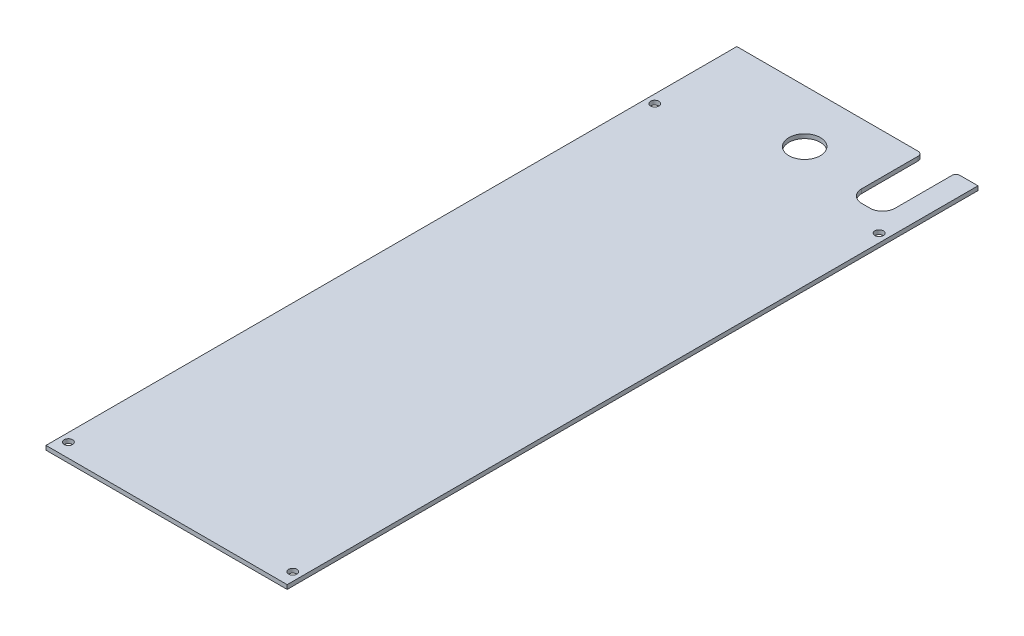
SolidWorks part; units mm, degrees
note: The reader was unsure of these and kept them because the rebuilt part matched: thickness of "Brida base2", "Chapa metálica(12)", "Chapa metálica(21)", "Chapa metálica(22)", "Chapa metálica(23)".
material "Poliestireno"
ref_plane "Alzado" through (0, 0, 0) normal (0, 0, 1) x (1, 0, 0)
ref_plane "Planta" through (0, 0, 0) normal (0, 1, 0) x (1, 0, 0)
ref_plane "Vista lateral" through (0, 0, 0) normal (1, 0, 0) x (0, 0, -1)
sketch "Croquis12" plane through (0, 0, 0) normal (0, 1, 0) x (1, 0, 0)
  line L0 (0, 0) -> (0, 121.41) construction
  line L1 (-57.5, -207.99) -> (57.5, -207.99)
  line L2 (-57.5, -207.99) -> (-57.5, 121.41)
  line L3 (-57.5, 121.41) -> (57.5, 121.41)
  line L4 (57.5, -207.99) -> (57.5, 121.41)
  point P14 (57.5, 121.41)
  point P17 (-57.5, 121.41)
  dimension "D1" = 115
  dimension "D2" = 207.99
  dimension "D3" = 121.41
base flange "Brida base2" sketch "Croquis12" thickness 2 reverse thickness direction no parameters "D1"=1
sketch "Croquis25" plane through (0, 0, 0) normal (0, 1, 0) x (1, 0, 0)
  line L0 (0, 0) -> (0, -48.7685) construction
  line L2 (-159.058, -201.3) -> (150.1867, -201.3) construction
  dimension "D2" = 201.3
sketch "Croquis27" plane through (0, 0, 0) normal (0, 1, 0) x (1, 0, 0)
  line L0 (0, 0) -> (0, -88.775) construction
  line L1 (-159.058, -201.3) -> (150.1867, -201.3) construction
  circle A0 centre (-53.5, -201.3) radius 2
  circle A1 centre (-53.5, 78.26) radius 2
  circle A2 centre (53.5, 78.26) radius 2
  circle A3 centre (53.5, -201.3) radius 2
  dimension "D1" = 4
  dimension "D4" = 107
  dimension "D2" = 78.26
extrude "Cortar-Extruir6" cut sketch "Croquis27" against normal up to next normal cut yes
sketch "Croquis28" plane through (0, 0, 0) normal (0, 1, 0) x (1, 0, 0)
  line L1 (-57.5, -207.99) -> (57.5, -207.99) construction
  circle A0 centre (0, 96.25) radius 7.5
  dimension "D1" = 304.24
  dimension "D2" = 15
extrude "Cortar-Extruir7" cut sketch "Croquis28" against normal up to next normal cut yes
sketch "Croquis29" plane through (0, 0, 0) normal (0, 1, 0) x (1, 0, 0)
  line L0 (39, 86.41) -> (39, 125.7663) construction
  line L1 (31, 121.41) -> (47, 121.41)
  line L2 (31, 121.41) -> (31, 86.41)
  line L3 (31, 86.41) -> (47, 86.41)
  line L4 (47, 121.41) -> (47, 86.41)
  line L5 (57.5, 121.41) -> (-57.5, 121.41) construction
  circle A0 centre (0, 96.25) radius 7.5 construction
  dimension "D1" = 39
  dimension "D2" = 16
  dimension "D3" = 35
extrude "Cortar-Extruir8" cut sketch "Croquis29" against normal through all normal cut yes
fillet "Redondeo1" radius 6 2 edges at (47, -1, -86.41) (31, -1, -86.41)
fillet "Redondeo2" radius 2 2 edges at (47, -1, -121.41) (31, -1, -121.41)
sketch "Líneas de pliegue3" plane through (0, 0, 0) normal (0, 1, 0) x (1, 0, 0)
sketch "Cuadro delimitador3" plane through (0, 0, 0) normal (0, 1, 0) x (1, 0, 0)
sheet metal parameters "Chapa metálica(12)" thickness 2 parameters "D1"=1
flat pattern "Chapa desplegada(12)" [suppressed]
sketch "Líneas de pliegue4" plane through (0, 0, 0) normal (0, 1, 0) x (1, 0, 0)
sketch "Cuadro delimitador4" [suppressed] plane through (0, 0, 0) normal (0, 1, 0) x (1, 0, 0)
sheet metal parameters "Chapa metálica(21)" thickness 2 parameters "D1"=1, "D7"=3
flat pattern "Chapa desplegada(12)"
sketch "Líneas de pliegue4" plane through (0, 0, 0) normal (0, 1, 0) x (1, 0, 0)
sketch "Cuadro delimitador4" [suppressed] plane through (0, 0, 0) normal (0, 1, 0) x (1, 0, 0)
sheet metal parameters "Chapa metálica(22)" thickness 2 parameters "D1"=1, "D7"=3
flat pattern "Chapa desplegada(12)"
sketch "Líneas de pliegue4" plane through (0, 0, 0) normal (0, 1, 0) x (1, 0, 0)
sketch "Cuadro delimitador4" [suppressed] plane through (0, 0, 0) normal (0, 1, 0) x (1, 0, 0)
sheet metal parameters "Chapa metálica(23)" thickness 2 parameters "D1"=1, "D7"=3
flat pattern "Chapa desplegada(12)"
sketch "Líneas de pliegue4" plane through (0, 0, 0) normal (0, 1, 0) x (1, 0, 0)
sketch "Cuadro delimitador4" [suppressed] plane through (0, 0, 0) normal (0, 1, 0) x (1, 0, 0)
